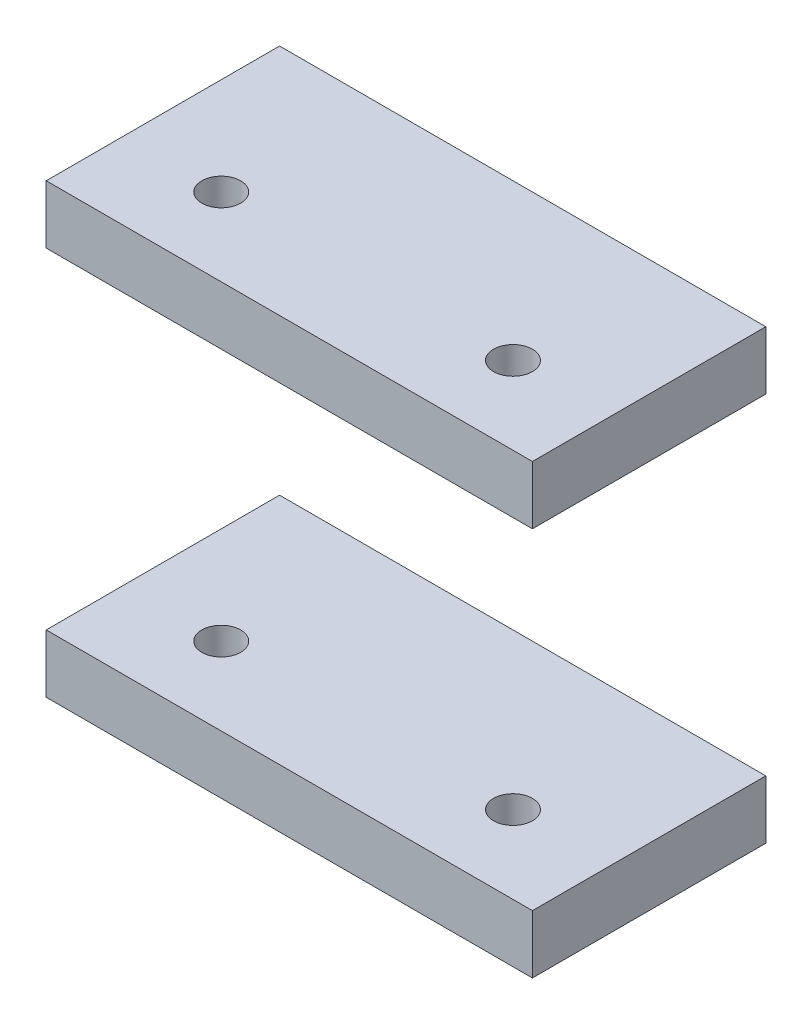
SolidWorks part; units mm, degrees
ref_plane "Front" through (0, 0, 0) normal (0, 0, 1) x (1, 0, 0)
ref_plane "Top" through (0, 0, 0) normal (0, 1, 0) x (1, 0, 0)
ref_plane "Right" through (0, 0, 0) normal (1, 0, 0) x (0, 0, -1)
sketch "草图1" plane through (0, 0, 0) normal (0, 0, 1) x (1, 0, 0)
  line L0 (25, -23) -> (-25, -23) construction
  line L1 (25, -23) -> (-25, -23)
  line L2 (25, 23) -> (-25, 23) construction
  line L3 (25, 23) -> (-25, 23)
  line L4 (25, -23) -> (25, 23) construction
  line L5 (-25, -23) -> (-25, 23) construction
  line L6 (25, -23) -> (25, -17)
  line L7 (-25, -23) -> (-25, -17)
  line L8 (-25, -17) -> (25, -17)
  line L9 (-25, 17) -> (25, 17)
  line L10 (-25, 17) -> (-25, 23)
  line L11 (25, 17) -> (25, 23)
  dimension "D1" = 6
  dimension "D2" = 6
extrude "凸台-拉伸1" add sketch "草图1" along normal blind 24 contours L8 L6 L1 L7 | L9 L11 L3 L10
sketch "草图2" plane through (0, -23, 0) normal (0, -1, 0) x (1, 0, 0)
  line L0 (25, 24) -> (-25, 24) construction
  line L1 (-25, 24) -> (-25, 0) construction
  circle A0 centre (-15, 16) radius 2
  circle A1 centre (15, 16) radius 2
  dimension "D1" = 4
  dimension "D2" = 30
  dimension "D3" = 8
  dimension "D4" = 10
extrude "切除-拉伸1" cut sketch "草图2" against normal through all
